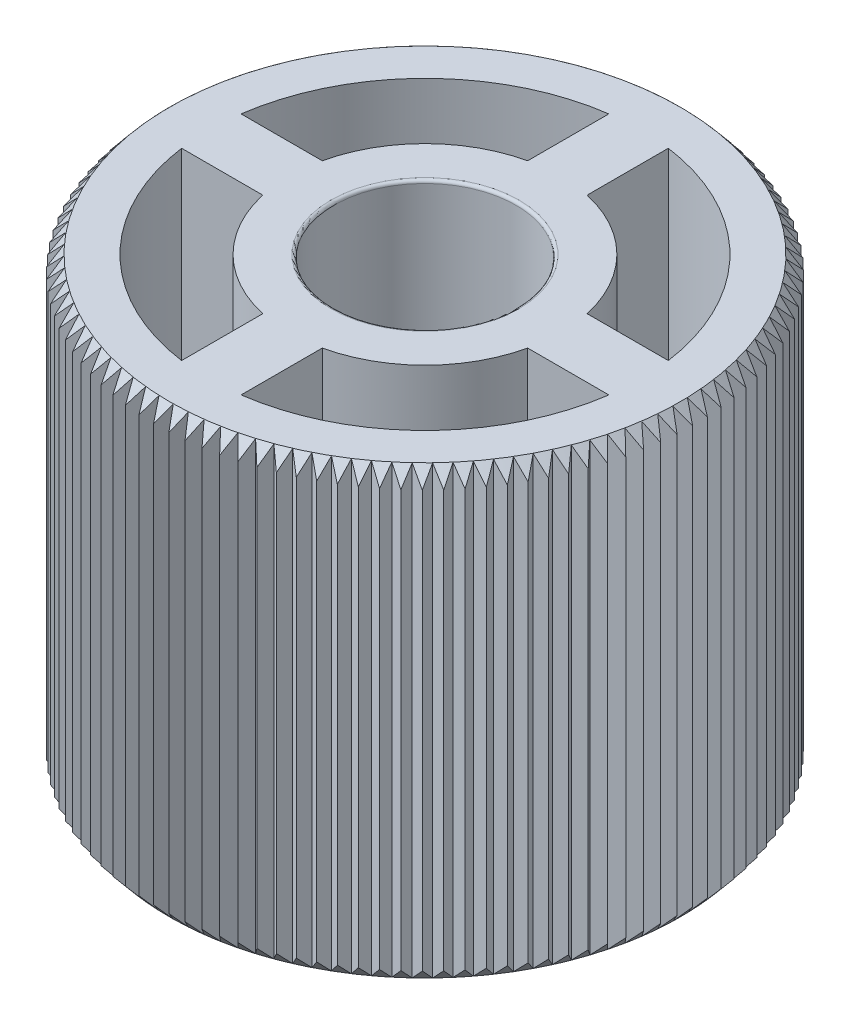
SolidWorks part; units mm, degrees
material "Alumina"
ref_plane "Front Plane" through (0, 0, 0) normal (0, 0, 1) x (1, 0, 0)
ref_plane "Top Plane" through (0, 0, 0) normal (0, 1, 0) x (1, 0, 0)
ref_plane "Right Plane" through (0, 0, 0) normal (1, 0, 0) x (0, 0, -1)
sketch "Sketch1" plane through (0, 0, 0) normal (0, 1, 0) x (1, 0, 0)
  line L0 (0, 9) -> (0, -9) construction
  line L1 (-9, 0) -> (9, 0) construction
  line L2 (0, 6.2803) -> (-1, 6.2803) construction
  line L3 (0, 6.2803) -> (1, 6.2803) construction
  line L4 (1, 4.4516) -> (1, 7.1807)
  line L5 (-1, 4.4516) -> (-1, 7.1807)
  line L6 (4.4516, 1) -> (7.1807, 1)
  line L7 (4.4516, -1) -> (7.1807, -1)
  line L8 (1, -4.4516) -> (1, -7.1807)
  line L9 (-1, -4.4516) -> (-1, -7.1807)
  line L10 (-4.4516, -1) -> (-7.1807, -1)
  line L11 (-4.4516, 1) -> (-7.1807, 1)
  line L12 (0, 0) -> (1, 4.4516) construction
  circle A0 centre (0, 0) radius 3.0625
  circle A1 centre (0, 0) radius 9
  circle A2 centre (0, 0) radius 7.25 construction
  circle A3 centre (0, 0) radius 4.5625 construction
  arc A4 (-4.4516, -1) -> (-1, -4.4516) centre (0, 0) ccw
  arc A5 (-7.1807, -1) -> (-1, -7.1807) centre (0, 0) ccw
  arc A6 (1, -7.1807) -> (7.1807, -1) centre (0, 0) ccw
  arc A7 (7.1807, 1) -> (1, 7.1807) centre (0, 0) ccw
  arc A8 (-1, 7.1807) -> (-7.1807, 1) centre (0, 0) ccw
  arc A9 (-4.4516, 1) -> (-1, 4.4516) centre (0, 0) cw
  arc A10 (1, 4.4516) -> (4.4516, 1) centre (0, 0) cw
  arc A11 (1, -4.4516) -> (4.4516, -1) centre (0, 0) ccw
  dimension "D1" = 6.125
  dimension "D2" = 18
  dimension "D3" = 9.125
  dimension "D4" = 14.5
  dimension "D5" = 1
  dimension "D6" = 4.5625
extrude "Boss-Extrude1" add sketch "Sketch1" along normal blind 7.5
sketch "Sketch2" plane through (0, 0, 0) normal (0, -1, 0) x (-1, 0, 0)
  circle A0 centre (0, 0) radius 9
extrude "Boss-Extrude2" add sketch "Sketch2" along normal blind 7.5
sketch "Sketch3" plane through (0, 0, 0) normal (0, 1, 0) x (1, 0, 0)
  circle A0 centre (0, 0) radius 1
extrude "Cut-Extrude1" cut sketch "Sketch3" against normal blind 2
sketch "Sketch4" plane through (0, -2, 0) normal (0, 1, 0) x (1, 0, 0)
  circle A0 centre (0, 0) radius 7.25
sketch "Sketch6" plane through (0, -7.5, 0) normal (0, -1, 0) x (1, 0, 0)
  line L0 (0, -1.023) -> (0, -6.9372) construction
  line L1 (0.5, -1.023) -> (0.5, -6.9372)
  line L2 (-0.5, -1.023) -> (-0.5, -6.9372)
  line L3 (0.5, -3.9801) -> (-0.5, -3.9801) construction
  arc A0 (0.5, -1.023) -> (-0.5, -1.023) centre (0, -1.023) ccw
  arc A1 (-0.5, -6.9372) -> (0.5, -6.9372) centre (0, -6.9372) ccw
  point P2 (0, -3.9801)
  dimension "D1" = 1
extrude "Cut-Extrude3" cut sketch "Sketch6" against normal blind 1
extrude "Cut-Extrude4" cut sketch "Sketch4" against normal blind 3.5
chamfer "Chamfer1" distance 0.5 angle 40 2 edges at (0, -7.5, -9) (0, 7.5, 9) first distance on face at (0, 7.5, 9)
fillet "Fillet3" radius 0.1 1 edges at (0, 7.5, 3.0625)
sketch "Sketch8" plane through (0, -7.5, 0) normal (0, -1, 0) x (-1, 0, 0)
  line L0 (0, 0) -> (-9, 0) construction
  line L1 (-9, 0) -> (-8.577, 0.2442)
  line L2 (-9, 0) -> (-8.577, -0.2442)
  line L3 (-8.9856, 0.5092) -> (-8.5494, 0.7291)
  line L4 (-8.9856, 0.5092) -> (-8.5771, 0.2414)
  line L5 (-8.9424, 1.0167) -> (-8.4945, 1.2116)
  line L6 (-8.9424, 1.0167) -> (-8.5497, 0.7263)
  line L7 (-8.8705, 1.521) -> (-8.4123, 1.6902)
  line L8 (-8.8705, 1.521) -> (-8.4949, 1.2088)
  line L9 (-8.7703, 2.0204) -> (-8.3032, 2.1635)
  line L10 (-8.7703, 2.0204) -> (-8.4129, 1.6875)
  line L11 (-8.6419, 2.5134) -> (-8.1675, 2.6297)
  line L12 (-8.6419, 2.5134) -> (-8.3039, 2.1607)
  line L13 (-8.4859, 2.9983) -> (-8.0057, 3.0876)
  line L14 (-8.4859, 2.9983) -> (-8.1684, 2.627)
  line L15 (-8.3027, 3.4735) -> (-7.8182, 3.5356)
  line L16 (-8.3027, 3.4735) -> (-8.0067, 3.085)
  line L17 (-8.0929, 3.9377) -> (-7.6056, 3.9722)
  line L18 (-8.0929, 3.9377) -> (-7.8193, 3.533)
  line L19 (-7.8571, 4.3893) -> (-7.3687, 4.3962)
  line L20 (-7.8571, 4.3893) -> (-7.6069, 3.9697)
  line L21 (-7.5962, 4.8267) -> (-7.1082, 4.806)
  line L22 (-7.5962, 4.8267) -> (-7.3702, 4.3937)
  line L23 (-7.311, 5.2488) -> (-6.8249, 5.2005)
  line L24 (-7.311, 5.2488) -> (-7.1098, 4.8037)
  line L25 (-7.0023, 5.654) -> (-6.5198, 5.5782)
  line L26 (-7.0023, 5.654) -> (-6.8266, 5.1982)
  line L27 (-6.6712, 6.0411) -> (-6.1937, 5.9382)
  line L28 (-6.6712, 6.0411) -> (-6.5216, 5.5761)
  line L29 (-6.3188, 6.4088) -> (-5.8479, 6.2791)
  line L30 (-6.3188, 6.4088) -> (-6.1957, 5.9361)
  line L31 (-5.9461, 6.7561) -> (-5.4832, 6.5999)
  line L32 (-5.9461, 6.7561) -> (-5.8499, 6.2771)
  line L33 (-5.5543, 7.0816) -> (-5.1011, 6.8995)
  line L34 (-5.5543, 7.0816) -> (-5.4854, 6.598)
  line L35 (-5.1448, 7.3845) -> (-4.7026, 7.177)
  line L36 (-5.1448, 7.3845) -> (-5.1034, 6.8978)
  line L37 (-4.7188, 7.6638) -> (-4.289, 7.4316)
  line L38 (-4.7188, 7.6638) -> (-4.7049, 7.1755)
  line L39 (-4.2776, 7.9185) -> (-3.8617, 7.6623)
  line L40 (-4.2776, 7.9185) -> (-4.2915, 7.4302)
  line L41 (-3.8228, 8.1478) -> (-3.422, 7.8685)
  line L42 (-3.8228, 8.1478) -> (-3.8642, 7.6611)
  line L43 (-3.3557, 8.351) -> (-2.9714, 8.0495)
  line L44 (-3.3557, 8.351) -> (-3.4246, 7.8674)
  line L45 (-2.8779, 8.5275) -> (-2.5112, 8.2048)
  line L46 (-2.8779, 8.5275) -> (-2.974, 8.0486)
  line L47 (-2.3908, 8.6766) -> (-2.043, 8.3337)
  line L48 (-2.3908, 8.6766) -> (-2.5139, 8.2039)
  line L49 (-1.8961, 8.798) -> (-1.5682, 8.4359)
  line L50 (-1.8961, 8.798) -> (-2.0457, 8.333)
  line L51 (-1.3953, 8.8912) -> (-1.0885, 8.5111)
  line L52 (-1.3953, 8.8912) -> (-1.571, 8.4354)
  line L53 (-0.8901, 8.9559) -> (-0.6052, 8.5591)
  line L54 (-0.8901, 8.9559) -> (-1.0913, 8.5108)
  line L55 (-0.382, 8.9919) -> (-0.12, 8.5796)
  line L56 (-0.382, 8.9919) -> (-0.608, 8.5589)
  line L57 (0.1274, 8.9991) -> (0.3656, 8.5727)
  line L58 (0.1274, 8.9991) -> (-0.1228, 8.5796)
  line L59 (0.6363, 8.9775) -> (0.85, 8.5382)
  line L60 (0.6363, 8.9775) -> (0.3627, 8.5728)
  line L61 (1.1432, 8.9271) -> (1.3317, 8.4765)
  line L62 (1.1432, 8.9271) -> (0.8472, 8.5385)
  line L63 (1.6464, 8.8481) -> (1.8091, 8.3876)
  line L64 (1.6464, 8.8481) -> (1.3289, 8.4769)
  line L65 (2.1443, 8.7408) -> (2.2807, 8.2718)
  line L66 (2.1443, 8.7408) -> (1.8063, 8.3882)
  line L67 (2.6354, 8.6055) -> (2.7451, 8.1295)
  line L68 (2.6354, 8.6055) -> (2.278, 8.2725)
  line L69 (3.118, 8.4426) -> (3.2006, 7.9612)
  line L70 (3.118, 8.4426) -> (2.7424, 8.1304)
  line L71 (3.5907, 8.2527) -> (3.6459, 7.7674)
  line L72 (3.5907, 8.2527) -> (3.198, 7.9622)
  line L73 (4.0518, 8.0363) -> (4.0795, 7.5486)
  line L74 (4.0518, 8.0363) -> (3.6433, 7.7686)
  line L75 (4.5, 7.7942) -> (4.5, 7.3058)
  line L76 (4.5, 7.7942) -> (4.077, 7.55)
  line L77 (4.9338, 7.5272) -> (4.9061, 7.0395)
  line L78 (4.9338, 7.5272) -> (4.4976, 7.3072)
  line L79 (5.3517, 7.236) -> (5.2965, 6.7506)
  line L80 (5.3517, 7.236) -> (4.9038, 7.0411)
  line L81 (5.7525, 6.9216) -> (5.67, 6.4402)
  line L82 (5.7525, 6.9216) -> (5.2943, 6.7524)
  line L83 (6.1349, 6.5851) -> (6.0252, 6.1091)
  line L84 (6.1349, 6.5851) -> (5.6678, 6.442)
  line L85 (6.4976, 6.2274) -> (6.3612, 5.7584)
  line L86 (6.4976, 6.2274) -> (6.0232, 6.1111)
  line L87 (6.8395, 5.8499) -> (6.6768, 5.3893)
  line L88 (6.8395, 5.8499) -> (6.3593, 5.7605)
  line L89 (7.1595, 5.4536) -> (6.971, 5.0029)
  line L90 (7.1595, 5.4536) -> (6.675, 5.3915)
  line L91 (7.4566, 5.0398) -> (7.2429, 4.6005)
  line L92 (7.4566, 5.0398) -> (6.9693, 5.0052)
  line L93 (7.7298, 4.6098) -> (7.4915, 4.1834)
  line L94 (7.7298, 4.6098) -> (7.2413, 4.6029)
  line L95 (7.9782, 4.1651) -> (7.7162, 3.7529)
  line L96 (7.9782, 4.1651) -> (7.4902, 4.1859)
  line L97 (8.2011, 3.7071) -> (7.9162, 3.3103)
  line L98 (8.2011, 3.7071) -> (7.715, 3.7554)
  line L99 (8.3977, 3.2372) -> (8.0908, 2.8572)
  line L100 (8.3977, 3.2372) -> (7.9151, 3.3129)
  line L101 (8.5673, 2.7569) -> (8.2395, 2.3948)
  line L102 (8.5673, 2.7569) -> (8.0898, 2.8598)
  line L103 (8.7096, 2.2678) -> (8.3618, 1.9249)
  line L104 (8.7096, 2.2678) -> (8.2387, 2.3976)
  line L105 (8.8239, 1.7714) -> (8.4573, 1.4487)
  line L106 (8.8239, 1.7714) -> (8.3611, 1.9276)
  line L107 (8.91, 1.2694) -> (8.5257, 0.9679)
  line L108 (8.91, 1.2694) -> (8.4568, 1.4515)
  line L109 (8.9676, 0.7633) -> (8.5668, 0.484)
  line L110 (8.9676, 0.7633) -> (8.5254, 0.9707)
  line L111 (8.9964, 0.2547) -> (8.5805, -0.0014)
  line L112 (8.9964, 0.2547) -> (8.5666, 0.4869)
  line L113 (8.9964, -0.2547) -> (8.5666, -0.4869)
  line L114 (8.9964, -0.2547) -> (8.5805, 0.0014)
  line L115 (8.9676, -0.7633) -> (8.5254, -0.9707)
  line L116 (8.9676, -0.7633) -> (8.5668, -0.484)
  line L117 (8.91, -1.2694) -> (8.4568, -1.4515)
  line L118 (8.91, -1.2694) -> (8.5257, -0.9679)
  line L119 (8.8239, -1.7714) -> (8.3611, -1.9276)
  line L120 (8.8239, -1.7714) -> (8.4573, -1.4487)
  line L121 (8.7096, -2.2678) -> (8.2387, -2.3976)
  line L122 (8.7096, -2.2678) -> (8.3618, -1.9249)
  line L123 (8.5673, -2.7569) -> (8.0898, -2.8598)
  line L124 (8.5673, -2.7569) -> (8.2395, -2.3948)
  line L125 (8.3977, -3.2372) -> (7.9151, -3.3129)
  line L126 (8.3977, -3.2372) -> (8.0908, -2.8572)
  line L127 (8.2011, -3.7071) -> (7.715, -3.7554)
  line L128 (8.2011, -3.7071) -> (7.9162, -3.3103)
  line L129 (7.9782, -4.1651) -> (7.4902, -4.1859)
  line L130 (7.9782, -4.1651) -> (7.7162, -3.7529)
  line L131 (7.7298, -4.6098) -> (7.2413, -4.6029)
  line L132 (7.7298, -4.6098) -> (7.4915, -4.1834)
  line L133 (7.4566, -5.0398) -> (6.9693, -5.0052)
  line L134 (7.4566, -5.0398) -> (7.2429, -4.6005)
  line L135 (7.1595, -5.4536) -> (6.675, -5.3915)
  line L136 (7.1595, -5.4536) -> (6.971, -5.0029)
  line L137 (6.8395, -5.8499) -> (6.3593, -5.7605)
  line L138 (6.8395, -5.8499) -> (6.6768, -5.3893)
  line L139 (6.4976, -6.2274) -> (6.0232, -6.1111)
  line L140 (6.4976, -6.2274) -> (6.3612, -5.7584)
  line L141 (6.1349, -6.5851) -> (5.6678, -6.442)
  line L142 (6.1349, -6.5851) -> (6.0252, -6.1091)
  line L143 (5.7525, -6.9216) -> (5.2943, -6.7524)
  line L144 (5.7525, -6.9216) -> (5.67, -6.4402)
  line L145 (5.3517, -7.236) -> (4.9038, -7.0411)
  line L146 (5.3517, -7.236) -> (5.2965, -6.7506)
  line L147 (4.9338, -7.5272) -> (4.4976, -7.3072)
  line L148 (4.9338, -7.5272) -> (4.9061, -7.0395)
  line L149 (4.5, -7.7942) -> (4.077, -7.55)
  line L150 (4.5, -7.7942) -> (4.5, -7.3058)
  line L151 (4.0518, -8.0363) -> (3.6433, -7.7686)
  line L152 (4.0518, -8.0363) -> (4.0795, -7.5486)
  line L153 (3.5907, -8.2527) -> (3.198, -7.9622)
  line L154 (3.5907, -8.2527) -> (3.6459, -7.7674)
  line L155 (3.118, -8.4426) -> (2.7424, -8.1304)
  line L156 (3.118, -8.4426) -> (3.2006, -7.9612)
  line L157 (2.6354, -8.6055) -> (2.278, -8.2725)
  line L158 (2.6354, -8.6055) -> (2.7451, -8.1295)
  line L159 (2.1443, -8.7408) -> (1.8063, -8.3882)
  line L160 (2.1443, -8.7408) -> (2.2807, -8.2718)
  line L161 (1.6464, -8.8481) -> (1.3289, -8.4769)
  line L162 (1.6464, -8.8481) -> (1.8091, -8.3876)
  line L163 (1.1432, -8.9271) -> (0.8472, -8.5385)
  line L164 (1.1432, -8.9271) -> (1.3317, -8.4765)
  line L165 (0.6363, -8.9775) -> (0.3627, -8.5728)
  line L166 (0.6363, -8.9775) -> (0.85, -8.5382)
  line L167 (0.1274, -8.9991) -> (-0.1228, -8.5796)
  line L168 (0.1274, -8.9991) -> (0.3656, -8.5727)
  line L169 (-0.382, -8.9919) -> (-0.608, -8.5589)
  line L170 (-0.382, -8.9919) -> (-0.12, -8.5796)
  line L171 (-0.8901, -8.9559) -> (-1.0913, -8.5108)
  line L172 (-0.8901, -8.9559) -> (-0.6052, -8.5591)
  line L173 (-1.3953, -8.8912) -> (-1.571, -8.4354)
  line L174 (-1.3953, -8.8912) -> (-1.0885, -8.5111)
  line L175 (-1.8961, -8.798) -> (-2.0457, -8.333)
  line L176 (-1.8961, -8.798) -> (-1.5682, -8.4359)
  line L177 (-2.3908, -8.6766) -> (-2.5139, -8.2039)
  line L178 (-2.3908, -8.6766) -> (-2.043, -8.3337)
  line L179 (-2.8779, -8.5275) -> (-2.974, -8.0486)
  line L180 (-2.8779, -8.5275) -> (-2.5112, -8.2048)
  line L181 (-3.3557, -8.351) -> (-3.4246, -7.8674)
  line L182 (-3.3557, -8.351) -> (-2.9714, -8.0495)
  line L183 (-3.8228, -8.1478) -> (-3.8642, -7.6611)
  line L184 (-3.8228, -8.1478) -> (-3.422, -7.8685)
  line L185 (-4.2776, -7.9185) -> (-4.2915, -7.4302)
  line L186 (-4.2776, -7.9185) -> (-3.8617, -7.6623)
  line L187 (-4.7188, -7.6638) -> (-4.7049, -7.1755)
  line L188 (-4.7188, -7.6638) -> (-4.289, -7.4316)
  line L189 (-5.1448, -7.3845) -> (-5.1034, -6.8978)
  line L190 (-5.1448, -7.3845) -> (-4.7026, -7.177)
  line L191 (-5.5543, -7.0816) -> (-5.4854, -6.598)
  line L192 (-5.5543, -7.0816) -> (-5.1011, -6.8995)
  line L193 (-5.9461, -6.7561) -> (-5.8499, -6.2771)
  line L194 (-5.9461, -6.7561) -> (-5.4832, -6.5999)
  line L195 (-6.3188, -6.4088) -> (-6.1957, -5.9361)
  line L196 (-6.3188, -6.4088) -> (-5.8479, -6.2791)
  line L197 (-6.6712, -6.0411) -> (-6.5216, -5.5761)
  line L198 (-6.6712, -6.0411) -> (-6.1937, -5.9382)
  line L199 (-7.0023, -5.654) -> (-6.8266, -5.1982)
  line L200 (-7.0023, -5.654) -> (-6.5198, -5.5782)
  line L201 (-7.311, -5.2488) -> (-7.1098, -4.8037)
  line L202 (-7.311, -5.2488) -> (-6.8249, -5.2005)
  line L203 (-7.5962, -4.8267) -> (-7.3702, -4.3937)
  line L204 (-7.5962, -4.8267) -> (-7.1082, -4.806)
  line L205 (-7.8571, -4.3893) -> (-7.6069, -3.9697)
  line L206 (-7.8571, -4.3893) -> (-7.3687, -4.3962)
  line L207 (-8.0929, -3.9377) -> (-7.8193, -3.533)
  line L208 (-8.0929, -3.9377) -> (-7.6056, -3.9722)
  line L209 (-8.3027, -3.4735) -> (-8.0067, -3.085)
  line L210 (-8.3027, -3.4735) -> (-7.8182, -3.5356)
  line L211 (-8.4859, -2.9983) -> (-8.1684, -2.627)
  line L212 (-8.4859, -2.9983) -> (-8.0057, -3.0876)
  line L213 (-8.6419, -2.5134) -> (-8.3039, -2.1607)
  line L214 (-8.6419, -2.5134) -> (-8.1675, -2.6297)
  line L215 (-8.7703, -2.0204) -> (-8.4129, -1.6875)
  line L216 (-8.7703, -2.0204) -> (-8.3032, -2.1635)
  line L217 (-8.8705, -1.521) -> (-8.4949, -1.2088)
  line L218 (-8.8705, -1.521) -> (-8.4123, -1.6902)
  line L219 (-8.9424, -1.0167) -> (-8.5497, -0.7263)
  line L220 (-8.9424, -1.0167) -> (-8.4945, -1.2116)
  line L221 (-8.9856, -0.5092) -> (-8.5771, -0.2414)
  line L222 (-8.9856, -0.5092) -> (-8.5494, -0.7291)
  line L223 (0, 0) -> (-8.577, 0.2442) construction
  circle A0 centre (0, 0) radius 9 construction
  circle A1 centre (0, 0) radius 8.5805 construction
  circle A2 centre (0, 0) radius 9.8996
  dimension "D1" = 60
  dimension "D2" = 8.5805
extrude "Cut-Extrude6" cut sketch "Sketch8" against normal blind 16 contours A2 L222 L221 L2 L1 L4 L3 L6 L5 L8 L7 L10 L9 L12 L11 L14 L13 L16 L15 L18 L17 L20 L19 L22 L21 L24 L23 L26 L25 L28 L27 L30 L29 L32 L31 L34 L33 L36 L35 L38 L37 L40 L39 L42 L41 L44 L43 L46 L45 L48 region at (9.6196, -7.5, 0)
